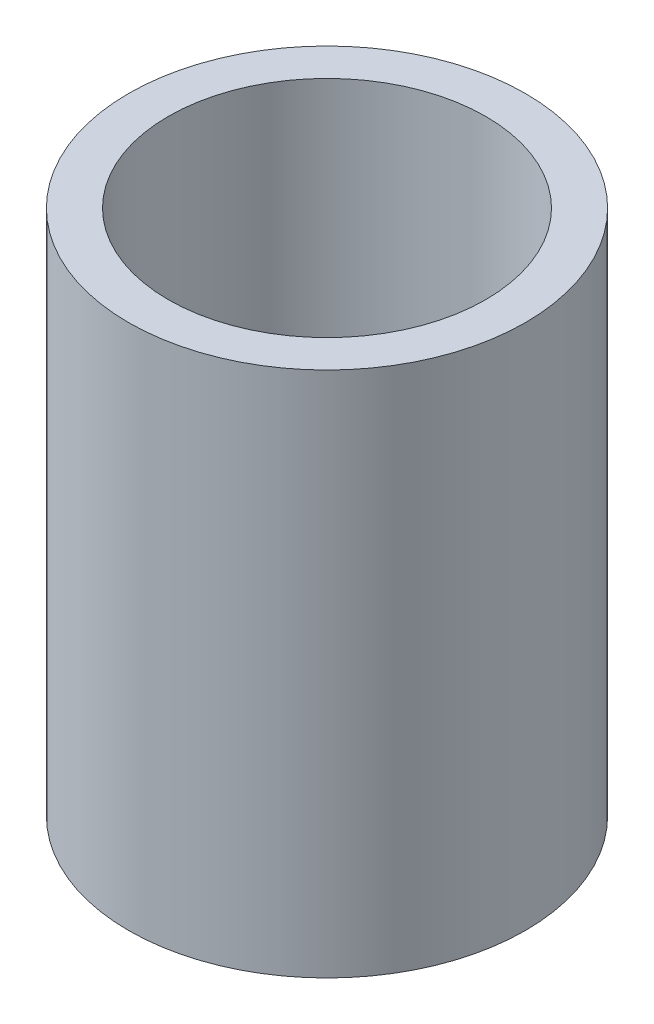
SolidWorks part; units mm, degrees
ref_plane "Płaszczyzna przednia" through (0, 0, 0) normal (0, 0, 1) x (1, 0, 0)
ref_plane "Płaszczyzna górna" through (0, 0, 0) normal (0, 1, 0) x (1, 0, 0)
ref_plane "Płaszczyzna prawa" through (0, 0, 0) normal (1, 0, 0) x (0, 0, -1)
sketch "Sketch1" plane through (0, 0, 0) normal (0, 0, 1) x (1, 0, 0)
  line L0 (0, 0) -> (0, 19.9) construction
  line L1 (6, 19.9) -> (0, 19.9) construction
  line L2 (6, 0) -> (7.5, 0)
  line L3 (6, 0) -> (6, 19.9)
  line L4 (6, 19.9) -> (7.5, 19.9)
  line L5 (7.5, 0) -> (7.5, 19.9)
  dimension "D1" = 6
  dimension "D2" = 1.5
  dimension "D3" = 19.9
revolve "Revolve1" add sketch "Sketch1" angle 360 about L0 region at (6.75, 9.95, 0)
